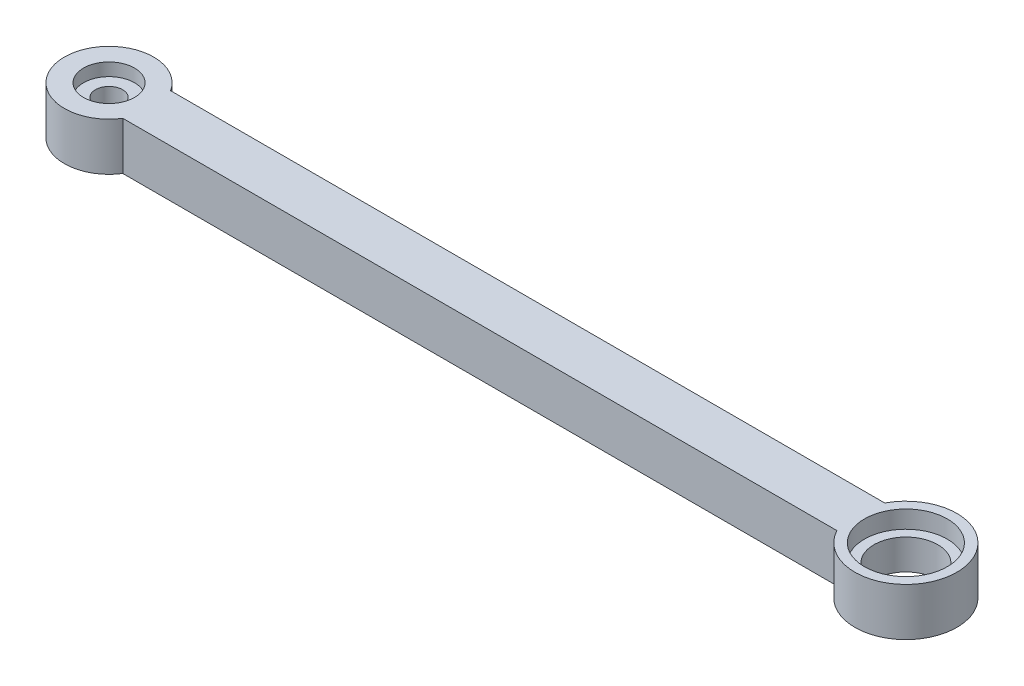
SolidWorks part; units mm, degrees
note: The reader was unsure of these and kept them because the rebuilt part matched: shared geometry of "Sketch2<9>", "Sketch2<11>", "Sketch2<13>".
ref_plane "Front Plane" through (0, 0, 0) normal (0, 0, 1) x (1, 0, 0)
ref_plane "Top Plane" through (0, 0, 0) normal (0, 1, 0) x (1, 0, 0)
ref_plane "Right Plane" through (0, 0, 0) normal (1, 0, 0) x (0, 0, -1)
sketch "Sketch2" plane through (0, 0, 0) normal (0, 1, 0) x (1, 0, 0)
  circle A0 centre (-50, 3.2206) radius 14
  circle A1 centre (200, 3.2206) radius 16
  circle A2 centre (200, 3.2206) radius 13
  circle A3 centre (200, 3.2206) radius 10
  circle A4 centre (-50, 3.2206) radius 8
  circle A5 centre (-50, 3.2206) radius 4.25
  dimension "D1" = 28
  dimension "D2" = 32
  dimension "D3" = 26
  dimension "D4" = 3
  dimension "D5" = 20
  dimension "D6" = 16
  dimension "D7" = 8.5
extrude "Boss-Extrude7" add sketch "Sketch2" along normal blind 15 contours A0
extrude "Boss-Extrude8" add sketch "Sketch2<9>" along normal blind 15 separate body contours A1
sketch "Sketch2<9>" plane through (0, 0, 0) normal (0, 1, 0) x (1, 0, 0) same geometry as "Sketch2"
extrude "Boss-Extrude9" add sketch "Sketch2<11>" along normal blind 9.5 contours A2 A3
sketch "Sketch2<11>" plane through (0, 0, 0) normal (0, 1, 0) x (1, 0, 0) same geometry as "Sketch2"
sketch "Sketch3" plane through (0, 0, 0) normal (1, 0, 0) x (0, 0, -1)
  line L0 (19.2206, 0) -> (19.2206, 15) construction
  line L1 (10.7206, 15) -> (-4.2794, 15)
  line L2 (10.7206, 15) -> (10.7206, 0)
  line L3 (10.7206, 0) -> (-4.2794, 0)
  line L4 (-4.2794, 15) -> (-4.2794, 0)
  line L5 (-12.7794, 15) -> (-12.7794, 0) construction
  line L6 (17.2206, 0) -> (17.2206, 15) construction
  line L7 (-1.2794, 12) -> (7.7206, 12)
  line L8 (-1.2794, 12) -> (-1.2794, 0)
  line L9 (-1.2794, 0) -> (7.7206, 0)
  line L10 (7.7206, 12) -> (7.7206, 0)
  line L11 (-10.7794, 15) -> (-10.7794, 0) construction
  dimension "D1" = 15
  dimension "D2" = 15
  dimension "D3" = 6.5
  dimension "D4" = 6.5
  dimension "D5" = 9
  dimension "D6" = 12
  dimension "D7" = 0
  dimension "D8" = 3
  dimension "D9" = 3
  dimension "D10" = 3
  dimension "D11" = 8.5
  dimension "D12" = 8.5
extrude "Boss-Extrude11" add sketch "Sketch3" against normal up to body and the other way up to body separate body contours L7 L10 L3 L2 L1 L4 L8
sketch "Sketch15" plane through (0, 0, -7.7206) normal (0, 0, 1) x (1, 0, 0)
  line L0 (-36.7429, 0) -> (184.6458, 0) construction
  line L1 (-15.9512, 12) -> (-12.9512, 12)
  line L2 (-15.9512, 12) -> (-15.9512, 2.5)
  line L3 (-15.9512, 2.5) -> (-12.9512, 2.5)
  line L4 (-12.9512, 12) -> (-12.9512, 2.5)
  line L5 (-38.1784, 0) -> (185.8667, 0) construction
  line L7 (84.9578, 12) -> (87.9578, 12)
  line L8 (12.2761, 12) -> (9.2761, 12)
  line L9 (12.2761, 12) -> (12.2761, 2.5)
  line L10 (12.2761, 2.5) -> (9.2761, 2.5)
  line L11 (9.2761, 12) -> (9.2761, 2.5)
  line L12 (34.5033, 12) -> (37.5033, 12)
  line L13 (34.5033, 12) -> (34.5033, 2.5)
  line L14 (34.5033, 2.5) -> (37.5033, 2.5)
  line L15 (37.5033, 12) -> (37.5033, 2.5)
  line L16 (59.7305, 12) -> (62.7305, 12)
  line L17 (59.7305, 12) -> (59.7305, 2.5)
  line L18 (59.7305, 2.5) -> (62.7305, 2.5)
  line L19 (62.7305, 12) -> (62.7305, 2.5)
  line L20 (-38.1784, 15) -> (-38.1784, 0) construction
  line L21 (84.9578, 12) -> (84.9578, 2.5)
  line L22 (84.9578, 2.5) -> (87.9578, 2.5)
  line L23 (87.9578, 12) -> (87.9578, 2.5)
  line L24 (110.185, 12) -> (113.185, 12)
  line L25 (110.185, 12) -> (110.185, 2.5)
  line L26 (110.185, 2.5) -> (113.185, 2.5)
  line L27 (113.185, 12) -> (113.185, 2.5)
  line L28 (135.4122, 12) -> (138.4122, 12)
  line L29 (135.4122, 12) -> (135.4122, 2.5)
  line L30 (135.4122, 2.5) -> (138.4122, 2.5)
  line L31 (138.4122, 12) -> (138.4122, 2.5)
  line L32 (160.6395, 12) -> (163.6395, 12)
  line L33 (160.6395, 12) -> (160.6395, 2.5)
  line L34 (160.6395, 2.5) -> (163.6395, 2.5)
  line L35 (163.6395, 12) -> (163.6395, 2.5)
  line L36 (185.8667, 0) -> (185.8667, 15) construction
  point P22 (10.7761, 2.5)
  dimension "D1" = 3
  dimension "D2" = 9.5
  dimension "D3" = 2.5
  dimension "D4" = 22.2272
  dimension "D5" = 22.2272
  dimension "D6" = 3
  dimension "D7" = 9.5
  dimension "D8" = 3
  dimension "D9" = 9.5
  dimension "D10" = 3
  dimension "D11" = 9.5
  dimension "D12" = 2.5
  dimension "D13" = 2.5
  dimension "D14" = 2.5
  dimension "D15" = 22.2272
  dimension "D16" = 22.2272
  dimension "D17" = 3
  dimension "D18" = 9.5
  dimension "D19" = 3
  dimension "D20" = 9.5
  dimension "D21" = 3
  dimension "D22" = 9.5
  dimension "D23" = 3
  dimension "D24" = 9.5
  dimension "D25" = 2.5
  dimension "D26" = 2.5
  dimension "D27" = 2.5
  dimension "D28" = 2.5
  dimension "D29" = 22.2272
  dimension "D30" = 22.2272
  dimension "D31" = 22.2272
  dimension "D32" = 22.2272
  dimension "D33" = 22.2272
extrude "Boss-Extrude12" add sketch "Sketch15" along normal up to next
fillet "Fillet1" radius 2 32 edges at (62.7305, 7.25, -7.7206) (62.7305, 7.25, 1.2794) (59.7305, 7.25, -7.7206) (59.7305, 7.25, 1.2794) (37.5033, 7.25, -7.7206) (37.5033, 7.25, 1.2794) (34.5033, 7.25, -7.7206) (34.5033, 7.25, 1.2794) (12.2761, 7.25, -7.7206) (12.2761, 7.25, 1.2794) (9.2761, 7.25, -7.7206) (9.2761, 7.25, 1.2794) (-12.9512, 7.25, -7.7206) (-12.9512, 7.25, 1.2794) (-15.9512, 7.25, -7.7206) (-15.9512, 7.25, 1.2794) (163.6395, 7.25, -7.7206) (163.6395, 7.25, 1.2794) (160.6395, 7.25, -7.7206) (160.6395, 7.25, 1.2794) (138.4122, 7.25, -7.7206) (138.4122, 7.25, 1.2794) (135.4122, 7.25, -7.7206) (135.4122, 7.25, 1.2794) (113.185, 7.25, -7.7206) (113.185, 7.25, 1.2794) (110.185, 7.25, -7.7206) (110.185, 7.25, 1.2794) (87.9578, 7.25, -7.7206) (87.9578, 7.25, 1.2794) (84.9578, 7.25, -7.7206) (84.9578, 7.25, 1.2794)
extrude "Boss-Extrude13" add sketch "Sketch2<13>" along normal blind 11 contours A4 A5
sketch "Sketch2<13>" plane through (0, 0, 0) normal (0, 1, 0) x (1, 0, 0) same geometry as "Sketch2"
